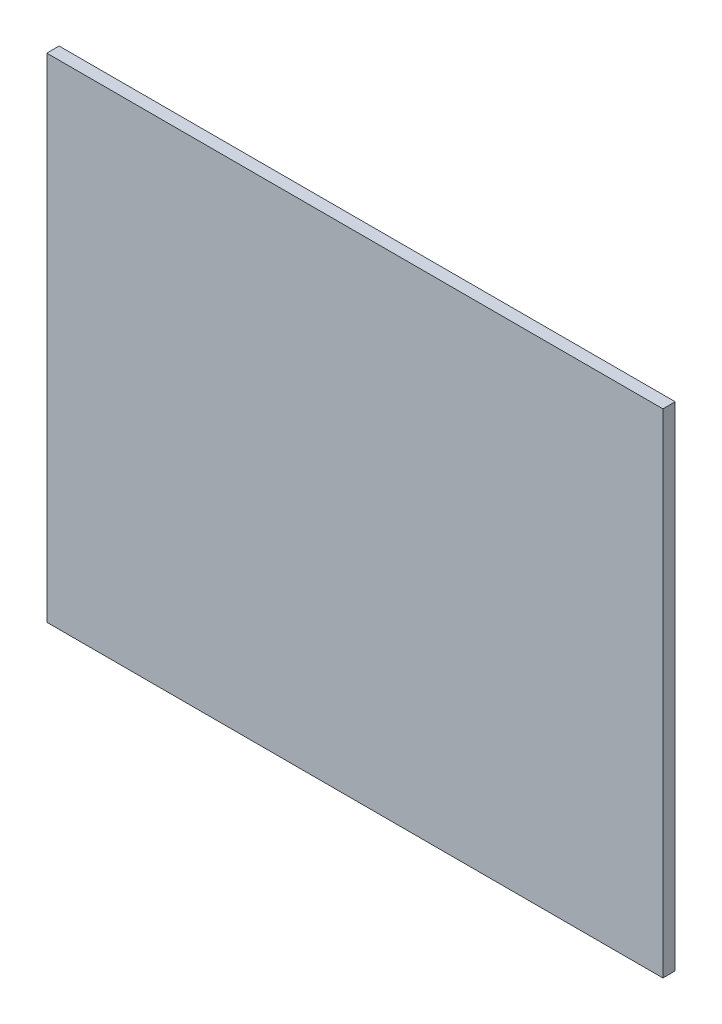
SolidWorks part; units mm, degrees
ref_plane "Plan de face" through (0, 0, 0) normal (0, 0, 1) x (1, 0, 0)
ref_plane "Plan de dessus" through (0, 0, 0) normal (0, 1, 0) x (1, 0, 0)
ref_plane "Plan de droite" through (0, 0, 0) normal (1, 0, 0) x (0, 0, -1)
sketch "Esquisse1" plane through (0, 0, 0) normal (0, 0, 1) x (1, 0, 0)
  line L1 (-250, -200) -> (250, -200)
  line L2 (-250, -200) -> (-250, 200)
  line L3 (-250, 200) -> (250, 200)
  line L4 (250, -200) -> (250, 200)
  line L5 (-250, -200) -> (250, 200) construction
  line L6 (-250, 200) -> (250, -200) construction
  point P0 (0, 0)
  dimension "D1" = 500
  dimension "D2" = 400
extrude "Boss.-Extru.1" add sketch "Esquisse1" along normal blind 10
sketch "Esquisse6" plane through (0, 0, 0) normal (0, 0, -1) x (-1, 0, 0)
  line L2 (0, 0) -> (85, 0) construction
  circle A3 centre (85, 0) radius 10
  dimension "D6" = 20
  dimension "D5" = 85
sketch "Esquisse7" plane through (0, 0, 0) normal (0, 0, 1) x (1, 0, 0)
  line L0 (0, 0) -> (0, 125) construction
  line L1 (0, 125) -> (85, 125) construction
  line L3 (0, 0) -> (0, -125) construction
  line L4 (0, -125) -> (85, -125) construction
  circle A4 centre (85, 125) radius 10
  circle A5 centre (85, -125) radius 10
  dimension "D1" = 125
  dimension "D2" = 125
  dimension "D4" = 85
  dimension "D7" = 20
  dimension "D8" = 20
  dimension "D3" = 85
